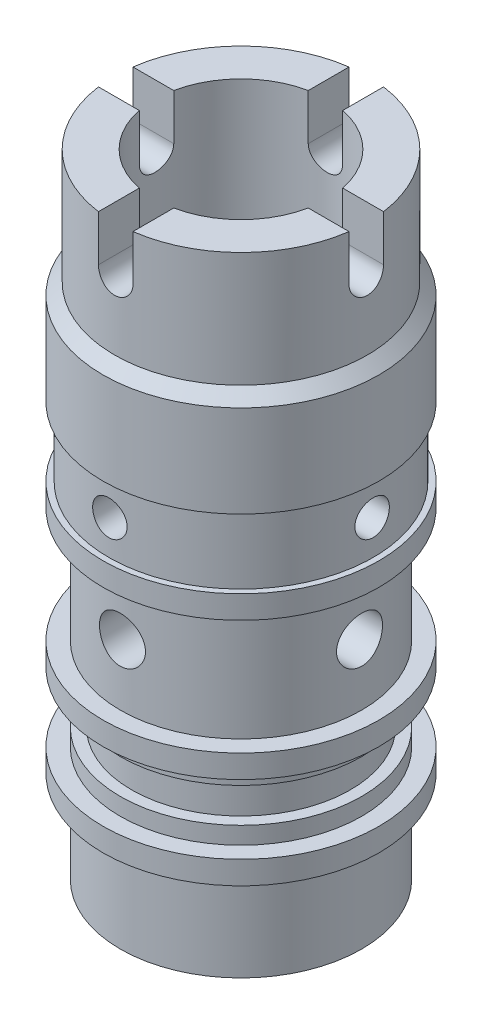
SolidWorks part; units mm, degrees
material "Plain Carbon Steel"
ref_plane "Front Plane" through (0, 0, 0) normal (0, 0, 1) x (1, 0, 0)
ref_plane "Top Plane" through (0, 0, 0) normal (0, 1, 0) x (1, 0, 0)
ref_plane "Right Plane" through (0, 0, 0) normal (1, 0, 0) x (0, 0, -1)
sketch "Sketch2" plane through (0, 0, 0) normal (0, 0, 1) x (1, 0, 0)
  line L0 (0, 27.5) -> (0, -27.5) construction
  line L1 (0, -27.5) -> (10.5, -27.5)
  line L2 (10.5, -27.5) -> (10.5, -19.5)
  line L3 (0, -19.5) -> (12, -19.5)
  line L4 (12, -19.5) -> (12, -17.5)
  line L5 (12, -17.5) -> (0, -17.5)
  line L6 (10.5, -17.5) -> (10.5, -11.5)
  line L7 (0, -11.5) -> (12, -11.5)
  line L8 (12, -11.5) -> (12, -9.5)
  line L9 (12, -9.5) -> (0, -9.5)
  line L10 (10.5, -9.5) -> (10.5, 0.5)
  line L11 (0, 0.5) -> (12, 0.5)
  line L12 (12, 0.5) -> (12, 2.5)
  line L13 (12, 2.5) -> (0, 2.5)
  line L15 (0, 8.5) -> (11.5, 8.5)
  line L16 (11.5, 8.5) -> (11.5, 2.5)
  line L18 (0, 17.5) -> (12, 17.5)
  line L19 (12, 17.5) -> (12, 8.5)
  line L20 (11.5, 8.5) -> (12, 8.5)
  line L22 (0, 27.5) -> (11, 27.5)
  line L23 (11, 27.5) -> (11, 17.5)
  point P4 (0, 0)
  dimension "D1" = 10.5
  dimension "D2" = 11
  dimension "D3" = 11.5
  dimension "D4" = 12
  dimension "D5" = 0.5
  dimension "D6" = 2.5
  dimension "D7" = 8.5
  dimension "D8" = 17.5
  dimension "D9" = 27.5
revolve "Revolve1" add sketch "Sketch2" angle 360 about L0 region at (5.5, 22.5, 0) region at (6, 13, 0) region at (5.75, 5.5, 0) region at (6, 1.5, 0) region at (5.25, -4.5, 0) region at (6, -10.5, 0) region at (5.25, -14.5, 0) region at (6, -18.5, 0) region at (5.25, -23.5, 0)
sketch "Sketch4" plane through (0, 0, 0) normal (0, 1, 0) x (1, 0, 0)
  circle A0 centre (0, 0) radius 7.5
extrude "Cut-Extrude1" cut sketch "Sketch4" against normal through all both and the other way through all
sketch "Sketch8" plane through (0, 0, 0) normal (0, 0, 1) x (1, 0, 0)
  circle A0 centre (0, -4.5) radius 2
  circle A1 centre (0, 5.5) radius 1.5
  dimension "D1" = 4
  dimension "D2" = 3
  dimension "D3" = 5.5
  dimension "D4" = 4.5
sketch "Sketch13" plane through (0, 0, 0) normal (0, 0, 1) x (1, 0, 0)
  line L1 (11, 27.5) -> (-11, 27.5) construction
  line L2 (-1.5, 23.5) -> (-1.5, 27.5)
  line L3 (1.5, 23.5) -> (1.5, 27.5)
  line L4 (7.5, 27.5) -> (-7.5, 27.5) construction
  arc A0 (-1.5, 23.5) -> (1.5, 23.5) centre (0, 23.5) ccw
  dimension "D1" = 1.5
  dimension "D2" = 23.5
extrude "Cut-Extrude4" cut sketch "Sketch13" against normal through all both and the other way through all contours L3 A0 L2
sketch "Sketch14" plane through (0, 0, 0) normal (0, 0, 1) x (1, 0, 0)
  line L0 (0, 27.5) -> (0, -27.1927) construction
  line L1 (0, -27.5) -> (0, -27.1927)
  line L2 (-10.5, -27.5) -> (10.5, -27.5) construction
  line L3 (-10.5132, -16) -> (0, -16) construction
  line L6 (-10.5132, -16) -> (-9.5132, -16)
  line L7 (-10.5132, -16) -> (-10.5132, -13)
  line L8 (-10.5132, -13) -> (-9.5132, -13)
  line L9 (-9.5132, -16) -> (-9.5132, -13)
  dimension "D1" = 3
  dimension "D2" = 1
  dimension "D3" = 9.5132
  dimension "D4" = 13
  dimension "D5" = 27.1927
pattern_circular "CirPattern1" count 4 over 360 about axis through (0, 27.5, 0) along (0, -1, 0) of "Cut-Extrude4"
extrude "Cut-Extrude5" cut sketch "Sketch8" against normal blind 10 and the other way through all contours A1
pattern_circular "CirPattern2" count 4 over 360 about axis through (0, 27.5, 0) along (0, -1, 0) of "Cut-Extrude5" reverse direction yes
sketch "Sketch15" plane through (0, 0, 0) normal (0, 0, 1) x (1, 0, 0)
  line L1 (0, 27.5) -> (0, -27.1927) construction
  circle A0 centre (0, -4.1927) radius 2
  dimension "D1" = 4
  dimension "D2" = 4.1927
extrude "Cut-Extrude6" cut sketch "Sketch15" against normal blind 10 and the other way through all
pattern_circular "CirPattern3" count 4 over 360 about axis through (0, 27.5, 0) along (0, -1, 0) of "Cut-Extrude6" reverse direction yes
sketch "Sketch23" plane through (0, 0, 0) normal (0, 0, 1) x (1, 0, 0)
  line L0 (0, -27.5) -> (0, -16) construction
  line L1 (-10.5, -27.5) -> (10.5, -27.5) construction
  line L2 (0, 27.5) -> (0, -27.1927) construction
revolve "Cut-Revolve2" cut sketch "Sketch14" angle 360 about L0 region at (-10.0132, -14.5, 0)
sketch "Sketch24" plane through (0, 0, 0) normal (0, 0, 1) x (1, 0, 0)
  line L0 (-12.9757, 15.5) -> (13.4271, 15.5) construction
  line L1 (-1.5, 27.5) -> (-7.3485, 27.5) construction
  line L2 (0, 28.7723) -> (0, -28.7723) construction
  line L12 (-9, 15.5) -> (-1.9877, 15.5)
  line L13 (-9, 15.5) -> (-9, 12.5)
  line L14 (-9, 12.5) -> (-1.9877, 12.5)
  line L15 (9, 15.5333) -> (9, 15.5)
  line L16 (0, 12.5) -> (0, 15.5) construction
  line L17 (-9, 14) -> (9, 14) construction
  line L18 (-1.9877, 15.5) -> (-1.9877, 12.5)
  point P4 (0, 14)
  point P7 (0, 0)
  dimension "D1" = 12
  dimension "D2" = 0
revolve "Cut-Revolve5" cut sketch "Sketch24" angle 360 about L2 region at (-5.4939, 14, 0) reverse direction yes
chamfer "Chamfer1" distance 1 angle 45 1 edges at (-12, 17.5, 0)
